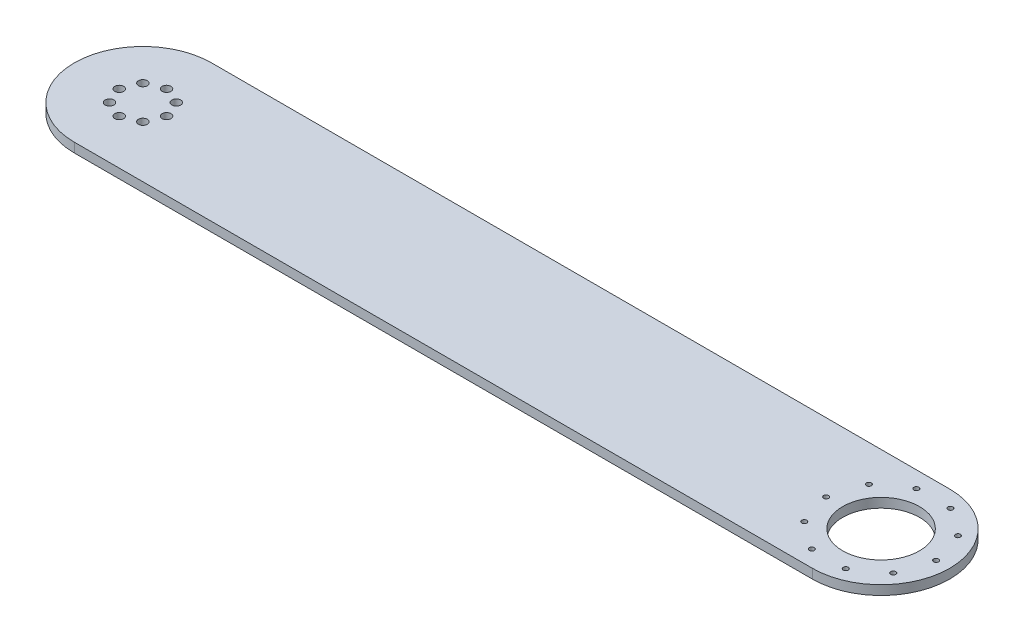
SolidWorks part; units mm, degrees
ref_plane "Front Plane" through (0, 0, 0) normal (0, 0, 1) x (1, 0, 0)
ref_plane "Top Plane" through (0, 0, 0) normal (0, 1, 0) x (1, 0, 0)
ref_plane "Right Plane" through (0, 0, 0) normal (1, 0, 0) x (0, 0, -1)
sketch "Sketch1" plane through (0, 0, 0) normal (0, 1, 0) x (1, 0, 0)
  line L0 (0, 0) -> (500, 0) construction
  line L1 (0, 46.5) -> (500, 46.5)
  line L2 (0, -46.5) -> (500, -46.5)
  arc A0 (0, 46.5) -> (0, -46.5) centre (0, 0) ccw
  arc A1 (500, -46.5) -> (500, 46.5) centre (500, 0) ccw
  circle A2 centre (0, 0) radius 16 construction
  circle A3 centre (-16, 0) radius 3
  circle A4 centre (-11.3137, 11.3137) radius 3
  circle A5 centre (0, 16) radius 3
  circle A6 centre (11.3137, 11.3137) radius 3
  circle A7 centre (16, 0) radius 3
  circle A8 centre (11.3137, -11.3137) radius 3
  circle A27 centre (500, 0) radius 37.25 construction
  circle A28 centre (537.25, 0) radius 1.7
  circle A29 centre (500, 0) radius 37.25 construction
  circle A30 centre (537.25, 0) radius 1.7
  circle A31 centre (530.1359, -21.895) radius 1.7
  circle A32 centre (511.5109, -35.4269) radius 1.7
  circle A33 centre (488.4891, -35.4269) radius 1.7
  circle A34 centre (469.8641, -21.895) radius 1.7
  circle A35 centre (462.75, 0) radius 1.7
  circle A36 centre (469.8641, 21.895) radius 1.7
  circle A37 centre (488.4891, 35.4269) radius 1.7
  circle A38 centre (511.5109, 35.4269) radius 1.7
  circle A39 centre (530.1359, 21.895) radius 1.7
  circle A40 centre (500, 0) radius 26
  circle A41 centre (0, -16) radius 3
  circle A42 centre (-11.3137, -11.3137) radius 3
  point P3 (250, 0)
  point P25 (0, 0)
  point P52 (500, 0)
  point P61 (500, 0)
  dimension "D3" = 32
  dimension "D4" = 6
  dimension "D2" = 74.5
  dimension "D7" = 3.4
  dimension "D8" = 3.4
  dimension "D10" = 52
  dimension "D6" = 46.5
  dimension "D1" = 500
  dimension "D5" = 8
  dimension "D9" = 10
extrude "Boss-Extrude1" add sketch "Sketch1" along normal blind 6.35 contours L2 A1 L1 A0 A40 A39 A38 A37 A36 A35 A34 A33 A32 A31 A28 A8 A7 A6 A5 A4 A3 region at (240.225, 0, 0)
equation "\"L1L\"=500"
equation "\"D1@Sketch1\"=\"L1L\""
equation "\"L1Thick\"=6.35"
equation "\"D1@Boss-Extrude1\"=\"L1Thick\""
equation "\"Harm-Drive-Outer\"=74.5"
equation "\"D2@Sketch1\"=\"Harm-Drive-Outer\""
